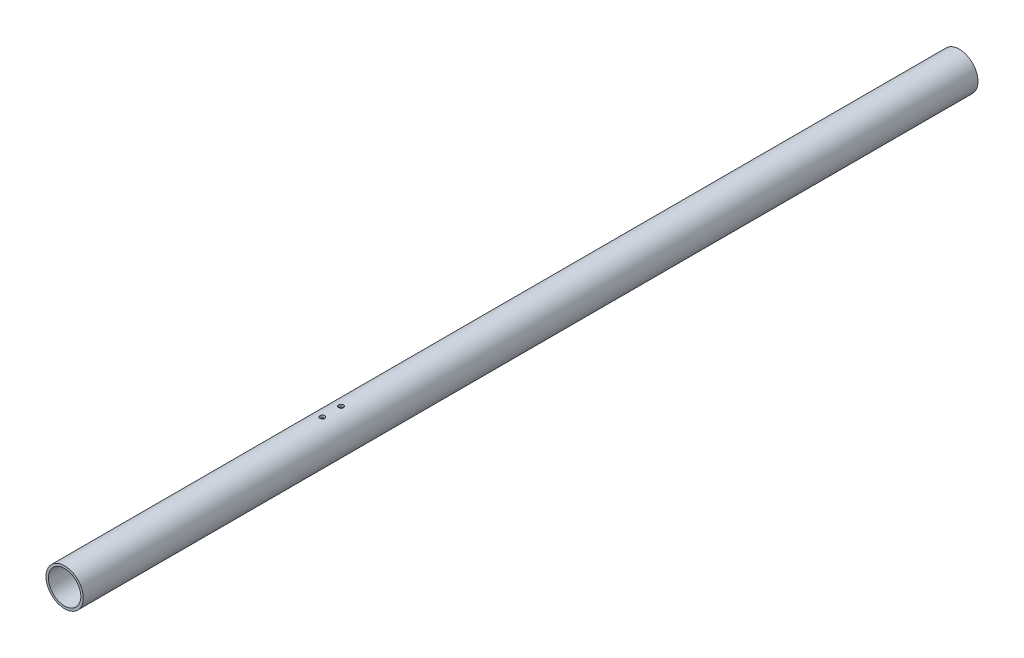
SolidWorks part; units mm, degrees
material "Acrylic (Medium-high impact)"
ref_plane "Front Plane" through (0, 0, 0) normal (0, 0, 1) x (1, 0, 0)
ref_plane "Top Plane" through (0, 0, 0) normal (0, 1, 0) x (1, 0, 0)
ref_plane "Right Plane" through (0, 0, 0) normal (1, 0, 0) x (0, 0, -1)
sketch "Sketch1" plane through (0, 0, 0) normal (0, 0, 1) x (1, 0, 0)
  circle A0 centre (0, 0) radius 12.7
  circle A1 centre (0, 0) radius 11.049
  dimension "D1" = 25.4
  dimension "D2" = 22.098
extrude "Boss-Extrude1" add sketch "Sketch1" along normal blind 609.6
sketch "Sketch2" plane through (0, 0, 0) normal (0, 0, 1) x (1, 0, 0)
  circle A0 centre (0, 0) radius 11.0998
  circle A1 centre (0, 0) radius 11.049
  dimension "D1" = 22.1996
  dimension "D2" = 22.098
extrude "Cut-Extrude1" cut sketch "Sketch2" along normal blind 76.2
sketch "Sketch3" plane through (0, 0, 0) normal (0, 0, -1) x (-1, 0, 0)
  circle A0 centre (0, 0) radius 12.7 construction
  point P0 (0, 12.7)
  point P1 (0, 0)
sketch "Sketch4" plane through (0, 0, 609.6) normal (0, 0, 1) x (1, 0, 0)
  circle A0 centre (0, 0) radius 12.7 construction
  point P0 (0, 12.7)
  point P1 (0, 0)
ref_plane "Plane1" through (0, -12.7, 0) normal (0, -1, 0) x (-1, 0, 0)
ref_axis "Axis1" through (0, 0, 76.2) along (0, 0, -1)
ref_plane "Plane2" through (0, 12.7, 0) normal (0, 1, 0) x (1, 0, 0)
sketch "Sketch5" plane through (0, 12.7, 0) normal (0, 1, 0) x (1, 0, 0)
  line L0 (12.7, 0) -> (-12.7, 0) construction
  line L1 (0, -609.6) -> (0, 0) construction
  circle A0 centre (0, -434.0225) radius 1.651
  circle A1 centre (0, -421.3225) radius 1.651
  point P0 (0, -421.3225)
  point P1 (0, -434.0225)
  dimension "D3" = 3.302
  dimension "D1" = 421.3225
  dimension "D2" = 12.7
extrude "Cut-Extrude2" cut sketch "Sketch5" against normal up to next
sketch "Sketch6" plane through (0, -12.7, 0) normal (0, -1, 0) x (-1, 0, 0)
  line L0 (11.0998, 0) -> (-11.0998, 0) construction
  line L1 (7.62, -292.1) -> (-7.62, -292.1)
  line L2 (7.62, -292.1) -> (7.62, -228.6)
  line L3 (7.62, -228.6) -> (-7.62, -228.6)
  line L4 (-7.62, -292.1) -> (-7.62, -228.6)
  line L5 (0, -292.1) -> (0, -228.6) construction
  line L6 (-12.7, -609.6) -> (12.7, -609.6) construction
  line L7 (0, 0) -> (0, -609.6) construction
  point P8 (0, -609.6)
  point P15 (0, 0)
  dimension "D1" = 63.5
  dimension "D2" = 292.1
  dimension "D3" = 15.24
extrude "Cut-Extrude3" cut sketch "Sketch6" against normal up to next
